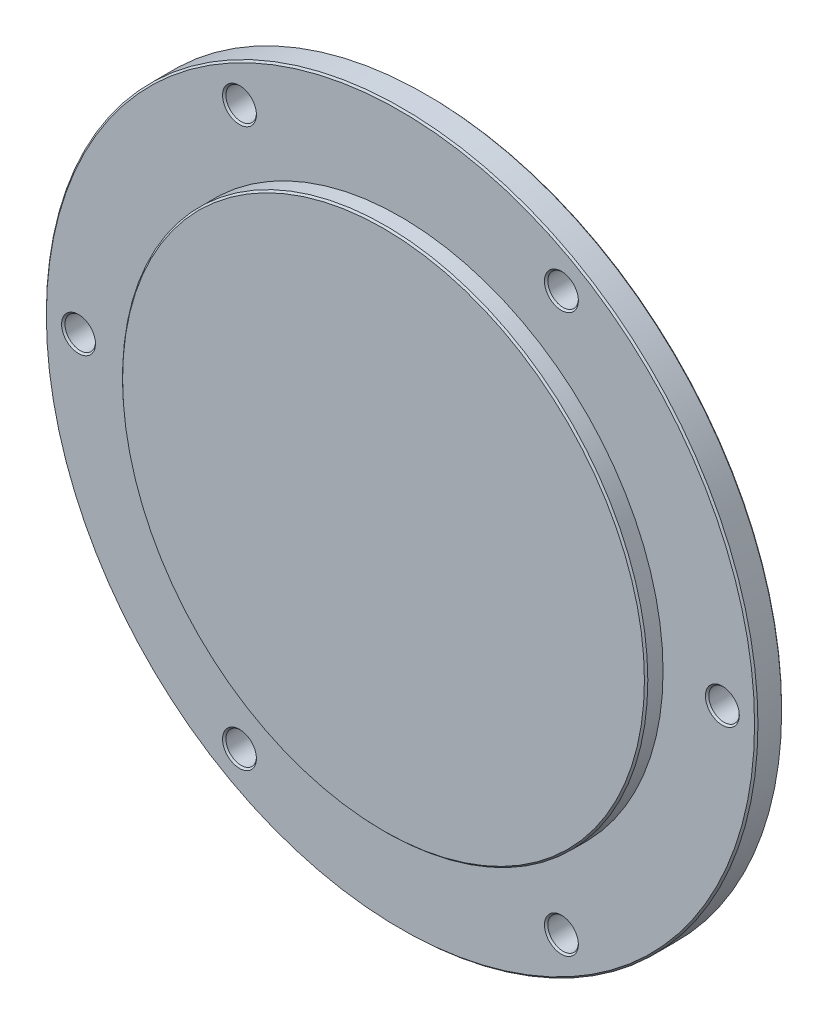
SolidWorks part; units mm, degrees
ref_plane "Front Plane" through (0, 0, 0) normal (0, 0, 1) x (1, 0, 0)
ref_plane "Top Plane" through (0, 0, 0) normal (0, 1, 0) x (1, 0, 0)
ref_plane "Right Plane" through (0, 0, 0) normal (1, 0, 0) x (0, 0, -1)
sketch "Sketch1" plane through (0, 0, 0) normal (0, 1, 0) x (1, 0, 0)
  line L0 (105, 0) -> (0, 0)
  line L1 (0, 0) -> (0, -8)
  line L2 (0, -8) -> (104.5, -8)
  line L3 (104.5, -8) -> (105, -7.5)
  line L4 (105, -7.5) -> (105, 0)
  line L5 (0, 0) -> (0, -8) construction
revolve "Revolve1" add sketch "Sketch1" angle 360 about L5 reverse direction yes
hole_wizard "Hole1" positions "Sketch3" profile "Sketch2" legacy
sketch "Sketch3" plane through (0, 0, 8) normal (0, 0, 1) x (1, 0, 0)
  point P0 (-47.5, -82.2724)
  point P1 (-47.5, 82.2724)
sketch "Sketch2" plane through (-47.5, -82.2724, 8) normal (1, 0, 0) x (0, -1, 0)
  line L0 (0, 0) -> (0, 8)
  line L1 (0, 8) -> (4.5, 8)
  line L2 (4.5, 8) -> (4.5, 0)
  line L3 (4.5, 0) -> (0, 0)
  line L4 (0, 110) -> (0, -10) construction
  dimension "Diameter" = 9
  dimension "Depth" = 8
hole_wizard "Hole2" positions "Sketch5" profile "Sketch4" legacy
sketch "Sketch5" plane through (0, 0, 0) normal (0, 0, -1) x (-1, 0, 0)
  point P0 (-47.5, -82.2724)
  point P1 (95, 0)
  point P2 (-47.5, 82.2724)
  point P3 (-95, 0)
sketch "Sketch4" plane through (47.5, -82.2724, 0) normal (1, 0, 0) x (0, 1, 0)
  line L0 (0, 0) -> (0, 8)
  line L1 (0, 8) -> (4.5, 8)
  line L2 (4.5, 8) -> (4.5, 0)
  line L3 (4.5, 0) -> (0, 0)
  line L4 (0, 110) -> (0, -10) construction
  dimension "Diameter" = 9
  dimension "Depth" = 8
sketch "Sketch6" plane through (0, 0, 8) normal (0, 0, 1) x (1, 0, 0)
  circle A0 centre (0, 0) radius 77.5
  dimension "D1" = 155
extrude "Boss-Extrude1" add sketch "Sketch6" along normal blind 5
chamfer "Chamfer1" distance 0.5 angle 45 14 edges at (43, -82.2724, 8) (90.5, 0, 8) (-99.5, 0, 8) (-43, -82.2724, 0) (43, -82.2724, 0) (-99.5, 0, 0) (-43, -82.2724, 8) (-43, 82.2724, 0) (43, 82.2724, 8) (43, 82.2724, 0) (105, 0, 0) (90.5, 0, 0) (-43, 82.2724, 8) (77.5, 0, 13)
